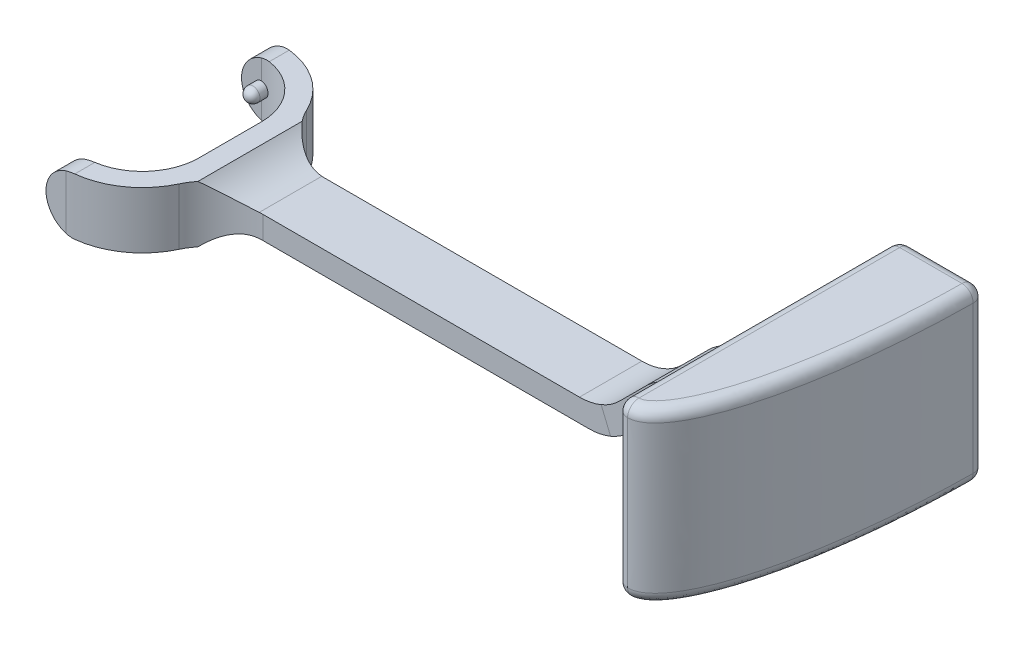
SolidWorks part; units mm, degrees
ref_plane "Front Plane" through (0, 0, 0) normal (0, 0, 1) x (1, 0, 0)
ref_plane "Top Plane" through (0, 0, 0) normal (0, 1, 0) x (1, 0, 0)
ref_plane "Right Plane" through (0, 0, 0) normal (1, 0, 0) x (0, 0, -1)
sketch "Sketch1" plane through (0, 0, 0) normal (1, 0, 0) x (0, 0, -1)
  line L1 (0, 0) -> (11, 0)
  line L2 (0, 0) -> (0, -4)
  line L3 (0, -4) -> (11, -4)
  line L4 (11, 0) -> (11, -4)
  dimension "D1" = 11
  dimension "D2" = 4
extrude "Boss-Extrude1" add sketch "Sketch1" along normal blind 62.5
ref_plane "Plane2" through (0, -3, 0) normal (0, 1, 0) x (1, 0, 0)
sketch3d "3DSketch3"
  line L0 (62.5, -3, -5.5) -> (72.5, -3, -5.5)
  line L1 (72.5, -3, -5.5) -> (83.1066, 7.6066, -5.5)
  line L2 (62.5, 0, -11) -> (62.5, 0, 0) construction
  line L3 (62.5, -4, -11) -> (62.5, 0, -11) construction
  line L4 (83.1066, 7.6066, -5.5) -> (93.1066, 7.6066, -5.5)
  dimension "D1" = 3
  dimension "D2" = 0
  dimension "D3" = 5.5
  dimension "D4" = 135
  dimension "D5" = 10
  dimension "D6" = 15
  dimension "D7" = 10
sketch "Sketch14" plane through (62.5, 0, 0) normal (1, 0, 0) x (0, 0, -1)
  line L1 (0, 0) -> (11, 0)
  line L2 (0, 0) -> (0, -4)
  line L3 (0, -4) -> (11, -4)
  line L4 (11, 0) -> (11, -4)
sweep "Sweep3" add profiles "Sketch14" path "3DSketch3"
fillet "Fillet1" radius 10 4 edges at (72.9142, -4, -5.5) (83.5208, 6.6066, -5.5) (81.864, 10.6066, -5.5) (71.2574, 0, -5.5)
sketch "Sketch16" plane through (93.1066, 0, 0) normal (1, 0, 0) x (0, 0, -1)
  line L1 (30.5, -7.3934) -> (-19.5, -7.3934)
  line L2 (30.5, -7.3934) -> (30.5, 22.6066)
  line L3 (30.5, 22.6066) -> (-19.5, 22.6066)
  line L4 (-19.5, -7.3934) -> (-19.5, 22.6066)
  line L9 (11, 10.6066) -> (0, 10.6066) construction
  line L10 (11, 6.6066) -> (11, 10.6066) construction
  dimension "D1" = 30
  dimension "D2" = 50
  dimension "D3" = 12
  dimension "D4" = 19.5
extrude "Boss-Extrude2" add sketch "Sketch16" along normal blind 15
fillet "Fillet2" radius 13 1 edges at (108.1066, 7.6066, 19.5) second distance 50 first distance on face at (100.6066, 7.6066, 19.5)
fillet "Fillet3" radius 2 13 edges at (93.1066, 8.6066, -11) (93.1066, 6.6066, -5.5) (93.1066, 8.6066, 0) (93.1066, 10.6066, -5.5) (93.1066, 7.6066, 19.5) (93.1066, -7.3934, -5.5) (93.1066, 22.6066, -5.5) (93.1066, 7.6066, -30.5)
sketch "Sketch17" plane through (0, 0, 0) normal (0, 1, 0) x (1, 0, 0)
  line L0 (-10, -10) -> (-13.5, -10)
  line L1 (-13.5, -10) -> (-13.5, -13.5)
  line L2 (-13.5, -13.5) -> (-10, -13.5)
  line L4 (-23.4629, 5.5) -> (20.4079, 5.5) construction
  line L5 (67.1152, 0) -> (0, 0) construction
  line L20 (3.5, 0) -> (3.5, 11)
  line L22 (-13.5, 24.5) -> (-10, 24.5)
  line L23 (0, 0) -> (0, 11)
  line L24 (-13.5, 21) -> (-13.5, 24.5)
  line L25 (-10, 21) -> (-13.5, 21)
  arc A0 (-10, -10) -> (0, 0) centre (-10, 0) ccw
  arc A2 (-10, -13.5) -> (3.5, 0) centre (-10, 0) ccw
  arc A3 (-10, 24.5) -> (3.5, 11) centre (-10, 11) cw
  arc A4 (-10, 21) -> (0, 11) centre (-10, 11) cw
  dimension "D3" = 20
  dimension "D6" = 3.5
  dimension "D1" = 0
  dimension "D2" = 10
  dimension "D5" = 3.5
  dimension "D7" = 5.5
extrude "Boss-Extrude3" add sketch "Sketch17" along normal blind 10 from offset 7 offset against normal yes
fillet "Fillet4" radius 10 2 edges at (3.5, -4, -5.5) (3.5, 0, -5.5)
fillet "Fillet5" radius 10 2 edges at (3.5, -2, 0) (3.5, -2, -11)
fillet "Fillet6" radius 5 4 edges at (-13.5, 3, 11.75) (-13.5, -7, 11.75) (-13.5, -7, -22.75) (-13.5, 3, -22.75)
sketch "Sketch18" plane through (0, 0, -21) normal (0, 0, 1) x (1, 0, 0)
  line L2 (-10, 2.7697) -> (-10, -6.7697) construction
  line L3 (0, 3) -> (-8.5, 3) construction
  circle A0 centre (-10, -2) radius 1.25
  dimension "D1" = 2.5
  dimension "D2" = 0
  dimension "D3" = 5
extrude "Boss-Extrude4" add sketch "Sketch18" along normal blind 1.5
sketch "Sketch19" plane through (0, 0, 10) normal (0, 0, -1) x (-1, 0, 0)
  line L0 (10, 2.7697) -> (10, -6.7697) construction
  circle A0 centre (10, -2) radius 1.25
  dimension "D1" = 2.5
  dimension "D2" = 5
extrude "Boss-Extrude5" add sketch "Sketch19" along normal blind 1.5
ref_plane "CenterOfClips" through (-7.5, 0, 0) normal (-1, 0, 0) x (0, 0, 1)
sketch "Sketch24" plane through (0, 0, 8.5) normal (0, 0, -1) x (-1, 0, 0)
  line L0 (10, -0.75) -> (10, -3.25)
  circle A0 centre (10, -2) radius 1.25 construction
  arc A1 (10, -3.25) -> (10, -0.75) centre (10, -2) ccw
revolve "Revolve9" add sketch "Sketch24" angle 180 about L0
sketch "Sketch25" plane through (0, 0, -19.5) normal (0, 0, 1) x (1, 0, 0)
  line L0 (-10, -0.75) -> (-10, -3.25)
  circle A0 centre (-10, -2) radius 1.25 construction
  arc A1 (-10, -0.75) -> (-10, -3.25) centre (-10, -2) ccw
revolve "Revolve10" add sketch "Sketch25" angle 180 about L0 reverse direction yes
